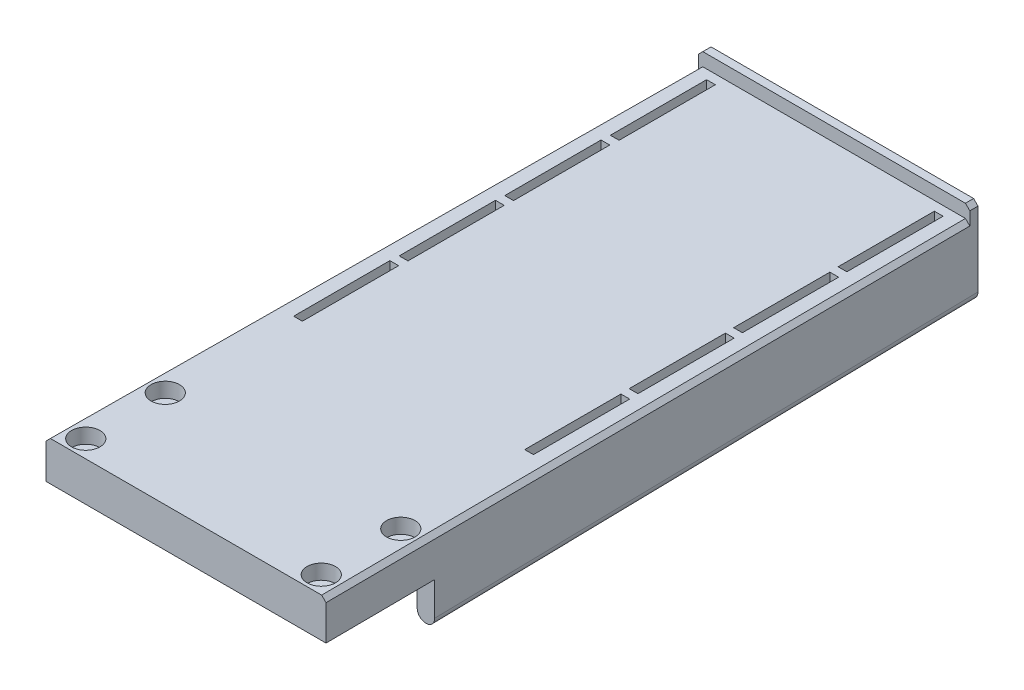
SolidWorks part; units mm, degrees
ref_plane "Front Plane" through (0, 0, 0) normal (0, 0, 1) x (1, 0, 0)
ref_plane "Top Plane" through (0, 0, 0) normal (0, 1, 0) x (1, 0, 0)
ref_plane "Right Plane" through (0, 0, 0) normal (1, 0, 0) x (0, 0, -1)
sketch "Sketch1" plane through (0, 0, 0) normal (0, 1, 0) x (1, 0, 0)
  line L0 (31, 0) -> (-31, 0)
  line L1 (0, 0) -> (0, -150) construction
  line L2 (32, -150) -> (-32, -150)
  line L3 (-32, -150) -> (-31, 0)
  line L4 (32, -150) -> (31, 0)
  dimension "\"neck length" = 150
extrude "Boss-Extrude1" add sketch "Sketch1" along normal blind 19
sketch "Sketch4" plane through (0, 0, 0) normal (1, 0, 0) x (0, 0, -1)
  line L0 (-150, 0) -> (0, 0)
  line L1 (0, 0) -> (0, 2)
  line L2 (0, 19) -> (0, 0) construction
  line L4 (0, 2) -> (-150, 0)
extrude "Cut-Extrude1" cut sketch "Sketch4" against normal through all both and the other way through all
shell "Shell1" thickness 4 removed face at (0, 1, 75)
fillet "Fillet2" 2 edges at (31.5, 1, 75) (27.4999, 1, 75) type full round first side face at (31.5, 10, 75) second side face at (27.4999, 5.5, 75) middle face at (0, 1, 75) tangent propagation no
fillet "Fillet3" 2 edges at (-31.5, 1, 75) (-27.4999, 1, 75) type full round first side face at (-31.5, 10, 75) second side face at (-27.4999, 5.5, 75) middle face at (0.0001, 1, 75) tangent propagation no
sketch "Sketch5" plane through (0, 19, 0) normal (0, 1, 0) x (1, 0, 0)
  line L0 (-31, 0) -> (-31.0125, -1.8797)
  line L1 (-31, 0) -> (-32, -150) construction
  line L2 (-31.0125, -1.8797) -> (31.0125, -1.8797)
  line L3 (32, -150) -> (31, 0) construction
  line L4 (31.0125, -1.8797) -> (31, 0)
  line L5 (31, 0) -> (-31, 0)
extrude "Boss-Extrude2" add sketch "Sketch5" along normal blind 3
chamfer "Chamfer1" distance 1 angle 45 2 edges at (31.5063, 19, 75.9398) (-31.5063, 19, 75.9398)
chamfer "Chamfer2" distance 1 angle 45 2 edges at (31.0063, 22, 0.9398) (-31.0063, 22, 0.9398)
sketch "Sketch6" plane through (0, 19, 0) normal (0, 1, 0) x (1, 0, 0)
  line L0 (-30.0125, -1.8797) -> (30.0125, -1.8797)
  line L1 (0, -1.8797) -> (0, -197.9912) construction
  line L2 (-31.316, -197.3975) -> (31.316, -197.3975)
  line L3 (31, -150) -> (30.0125, -1.8797) construction
  line L4 (31.316, -197.3975) -> (30.0125, -1.8797)
  line L5 (-30.0125, -1.8797) -> (-31.316, -197.3975)
  line L6 (-30.0125, -1.8797) -> (-31, -150) construction
extrude "Cut-Extrude2" [suppressed] cut sketch "Sketch6" against normal blind 1.6
sketch "Sketch7" plane through (0, 0, 150) normal (0, 0, 1) x (1, 0, 0)
  line L1 (-32, 10) -> (32, 10)
  line L2 (-32, 18) -> (-32, 2) construction
  line L3 (32, 18) -> (32, 2) construction
  line L4 (32, 10) -> (32, 0)
  line L7 (-32, 0) -> (-32, 10)
  line L8 (-32, 0) -> (32, 0)
extrude "Cut-Extrude3" cut sketch "Sketch7" against normal blind 25
sketch "Sketch11" plane through (0, 10, 0) normal (0, -1, 0) x (1, 0, 0)
  line L0 (27.1522, 27.9997) -> (27.1522, 49.9997)
  line L1 (27.0266, 4) -> (25.0266, 4)
  line L2 (27.0266, 4) -> (27.0266, 26)
  line L3 (27.0266, 26) -> (25.0266, 26)
  line L4 (25.0266, 4) -> (25.0266, 26)
  line L5 (27.1522, 27.9997) -> (25.1522, 27.9997)
  line L6 (25.1522, 27.9997) -> (25.1522, 49.9997)
  line L7 (27.1522, 49.9997) -> (25.1522, 49.9997)
  line L8 (27.2779, 51.9993) -> (27.2779, 73.9993)
  line L9 (27.2779, 51.9993) -> (25.2779, 51.9993)
  line L10 (25.2779, 51.9993) -> (25.2779, 73.9993)
  line L11 (27.2779, 73.9993) -> (25.2779, 73.9993)
  line L12 (27.4036, 75.999) -> (27.4036, 97.999)
  line L13 (27.4036, 75.999) -> (25.4036, 75.999)
  line L14 (25.4036, 75.999) -> (25.4036, 97.999)
  line L15 (27.4036, 97.999) -> (25.4036, 97.999)
  line L16 (27.0266, 4) -> (27.1522, 27.9997) construction
  line L17 (0, -11.9167) -> (0, 11.9167) construction
  line L18 (-27.4036, 75.999) -> (-25.4036, 75.999)
  line L19 (-25.4036, 75.999) -> (-25.4036, 97.999)
  line L20 (-27.4036, 97.999) -> (-25.4036, 97.999)
  line L21 (-27.4036, 75.999) -> (-27.4036, 97.999)
  line L22 (-27.2779, 51.9993) -> (-25.2779, 51.9993)
  line L23 (-25.2779, 51.9993) -> (-25.2779, 73.9993)
  line L24 (-27.2779, 73.9993) -> (-25.2779, 73.9993)
  line L25 (-27.2779, 51.9993) -> (-27.2779, 73.9993)
  line L26 (-27.1522, 27.9997) -> (-25.1522, 27.9997)
  line L27 (-25.1522, 27.9997) -> (-25.1522, 49.9997)
  line L28 (-27.1522, 49.9997) -> (-25.1522, 49.9997)
  line L29 (-27.1522, 27.9997) -> (-27.1522, 49.9997)
  line L30 (-27.0266, 26) -> (-25.0266, 26)
  line L31 (-25.0266, 4) -> (-25.0266, 26)
  line L32 (-27.0266, 4) -> (-25.0266, 4)
  line L33 (-27.0266, 4) -> (-27.0266, 26)
  dimension "D1" = 22
  dimension "D2" = 2
  dimension "D4" = 24
  dimension "D3" = 4
extrude "Cut-Extrude4" cut sketch "Sketch11" against normal through all
hole_wizard "CBORE for M3 Hex Socket Head Cap Screw1" positions "Sketch12" profile "Sketch13" counterbore size "M3" standard "ISO" end condition through all
sketch "Sketch12" plane through (75.2969, 19, 61.2992) normal (0, 1, 0) x (1, 0, 0)
  point P0 (-102.2096, -66.5318)
  point P1 (-102.2096, -84.7008)
  point P2 (-48.3841, -84.7008)
  point P3 (-48.3841, -66.5318)
sketch "Sketch13" plane through (-26.9127, 19, 127.831) normal (1, 0, 0) x (0, 0, 1)
  line L0 (0, 0) -> (0, 18.6667)
  line L1 (0, 18.6667) -> (1.45, 18.6667)
  line L2 (1.45, 18.6667) -> (1.45, 3.4)
  line L3 (1.45, 3.4) -> (3.25, 3.4)
  line L4 (3.25, 3.4) -> (3.25, 0)
  line L5 (3.25, 0) -> (0, 0)
  line L6 (0, -6.35) -> (0, 107.95) construction
  dimension "Thru Hole Dia." = 2.9
  dimension "Thru Hole Depth" = 18.6667
  dimension "C'Bore Dia." = 6.5
  dimension "C'Bore Depth" = 3.4
sketch "Sketch14" plane through (0, 10, 0) normal (0, -1, 0) x (1, 0, 0)
  line L0 (-17.0266, 8.2928) -> (-17.0266, 78.2928)
  line L1 (-17.0266, 8.2928) -> (-8.5133, 8.2928)
  line L2 (-8.5133, 8.2928) -> (-8.5133, 78.2928)
  line L3 (-8.5133, 78.2928) -> (0, 78.2928)
  line L4 (0, 78.2928) -> (0, 8.2928)
  line L5 (0, 8.2928) -> (8.5133, 8.2928)
  line L6 (8.5133, 8.2928) -> (8.5133, 78.2928)
  line L7 (8.5133, 78.2928) -> (17.0266, 78.2928)
  line L8 (17.0266, 78.2928) -> (17.0266, 8.2928)
  line L9 (-27.0266, 26) -> (-27.0266, 4) construction
  line L10 (27.0266, 4) -> (27.0266, 26) construction
  dimension "D1" = 70
  dimension "D2" = 10
  dimension "D3" = 10
equation "\"neck length\"= 200mm"
equation "\"stringLength\"=69.2489"
